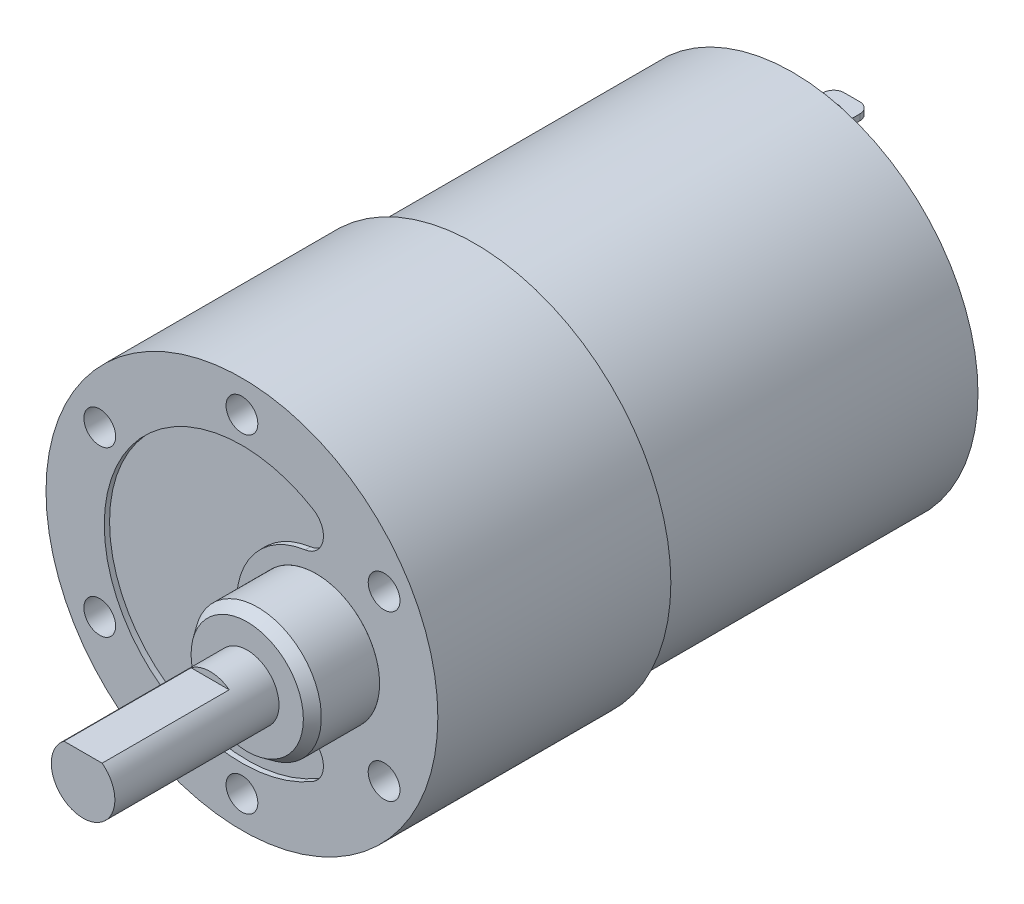
SolidWorks part; units mm, degrees
ref_plane "Front Plane" through (0, 0, 0) normal (0, 0, 1) x (1, 0, 0)
ref_plane "Top Plane" through (0, 0, 0) normal (0, 1, 0) x (1, 0, 0)
ref_plane "Right Plane" through (0, 0, 0) normal (1, 0, 0) x (0, 0, -1)
sketch "Sketch1" plane through (0, 0, 0) normal (0, 0, 1) x (1, 0, 0)
  circle A0 centre (0, 0) radius 18.5
  dimension "D1" = 37
extrude "Boss-Extrude1" add sketch "Sketch1" against normal blind 22
sketch "Sketch2" plane through (0, 0, -22) normal (0, 0, -1) x (-1, 0, 0)
  circle A0 centre (0, 0) radius 17.5
  dimension "D1" = 35
extrude "Boss-Extrude2" add sketch "Sketch2" along normal blind 30
sketch "Sketch3" plane through (0, 0, -52) normal (0, 0, -1) x (-1, 0, 0)
  circle A0 centre (0, 0) radius 4.5
  dimension "D1" = 9
extrude "Boss-Extrude3" add sketch "Sketch3" along normal blind 1
fillet "Fillet1" radius 1 1 edges at (-4.5, 0, -53)
sketch "Sketch4" plane through (0, 0, -52) normal (0, 0, -1) x (-1, 0, 0)
  line L1 (-1.7368, 12.657) -> (1.7368, 12.657)
  line L2 (-1.7368, 12.657) -> (-1.7368, 12.086)
  line L3 (-1.7368, 12.086) -> (1.7368, 12.086)
  line L4 (1.7368, 12.657) -> (1.7368, 12.086)
  line L5 (-1.7368, 12.657) -> (1.7368, 12.086) construction
  line L6 (-1.7368, 12.086) -> (1.7368, 12.657) construction
  point P0 (0, 12.3715)
extrude "Boss-Extrude4" add sketch "Sketch4" along normal blind 5.6
fillet "Fillet2" radius 1 2 edges at (-1.7368, 12.3715, -57.6) (1.7368, 12.3715, -57.6)
sketch "Sketch5" plane through (0, 12.657, 0) normal (0, 1, 0) x (1, 0, 0)
  circle A0 centre (0, 55.7146) radius 0.6187
extrude "Cut-Extrude1" cut sketch "Sketch5" against normal up to next
mirror "Mirror1" about plane through (0, 0, 0) normal (0, 1, 0) of "Cut-Extrude1", "Fillet2", "Boss-Extrude4"
sketch "Sketch6" plane through (0, 0, 0) normal (0, 0, 1) x (1, 0, 0)
  circle A0 centre (0, 0) radius 15.5 construction
  dimension "D1" = 31
sketch "Sketch7" plane through (0, 0, 0) normal (0, 0, 1) x (1, 0, 0)
  circle A0 centre (0, 15.5) radius 1.5
  circle A1 centre (0, 0) radius 15.5 construction
  dimension "D1" = 3
extrude "Cut-Extrude2" cut sketch "Sketch7" against normal blind 25.4
pattern_circular "CirPattern1" count 6 over 360 about axis through (0, 0, 0) along (0, 0, 1) of "Cut-Extrude2"
sketch "Sketch8" plane through (0, 0, 0) normal (0, 0, 1) x (1, 0, 0)
  circle A0 centre (7, 0) radius 6
  dimension "D1" = 12
  dimension "D2" = 7
extrude "Boss-Extrude5" add sketch "Sketch8" along normal blind 6.5
chamfer "Chamfer1" distance 1 angle 35 1 edges at (13, 0, 6.5) first distance on face at (13, 0, 6.5)
sketch "Sketch9" plane through (0, 0, 6.5) normal (0, 0, 1) x (1, 0, 0)
  circle A0 centre (7, 0) radius 3
  dimension "D1" = 6
extrude "Boss-Extrude6" add sketch "Sketch9" along normal blind 15.5
sketch "Sketch10" plane through (0, 0, 22) normal (0, 0, 1) x (1, 0, 0)
  line L0 (7, -3) -> (7, 2.4) construction
  line L1 (4.4062, 2.4) -> (9.5938, 2.4)
  line L2 (4.4062, 2.4) -> (4.4062, 3.5726)
  line L3 (4.4062, 3.5726) -> (9.5938, 3.5726)
  line L4 (9.5938, 3.5726) -> (9.5938, 2.4)
  circle A0 centre (7, 0) radius 3 construction
  dimension "D1" = 5.4
extrude "Cut-Extrude3" cut sketch "Sketch10" against normal blind 12
sketch "Sketch11" plane through (0, 0, 0) normal (0, 0, 1) x (1, 0, 0)
  arc A0 (6.7321, 11.1211) -> (6.7321, -11.1211) centre (0, 0) ccw
  circle A1 centre (7, 0) radius 6 construction
  circle A2 centre (7, 0) radius 6
  arc A3 (5.9709, 7.4291) -> (5.9709, -7.4291) centre (7, 0) ccw
  circle A4 centre (7, 0) radius 7.5 construction
  arc A5 (5.9709, -7.4291) -> (6.7321, -11.1211) centre (5.6964, -9.4101) cw
  arc A6 (5.9709, 7.4291) -> (6.7321, 11.1211) centre (5.6964, 9.4101) ccw
  dimension "D2" = 2
  dimension "D1" = 1.5
extrude "Cut-Extrude4" cut sketch "Sketch11" against normal blind 0.5
